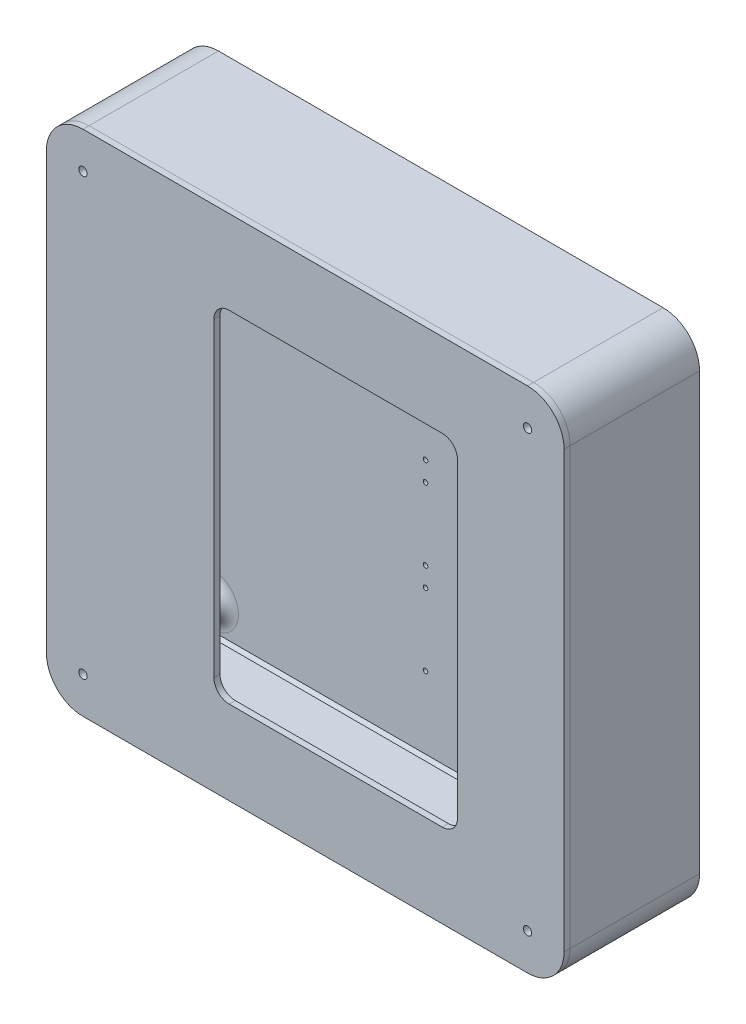
SolidWorks part; units mm, degrees
ref_plane "Front Plane" through (0, 0, 0) normal (1, 0, 0) x (0, 1, 0)
ref_plane "Top Plane" through (0, 0, 0) normal (0, 0, 1) x (0, 1, 0)
ref_plane "Right Plane" through (0, 0, 0) normal (0, 1, 0) x (-1, 0, 0)
sketch "Sketch1" plane through (0, 0, 0) normal (0, 0, 1) x (0, 1, 0)
  line L0 (-6.375, 0) -> (6.375, 0) construction
  line L1 (-113.625, 0) -> (-66.375, 0) construction
  line L2 (66.375, 0) -> (113.625, 0) construction
  line L3 (-167, 164) -> (167, 164)
  line L4 (-163, 160) -> (163, 160)
  line L5 (-163, 160) -> (-163, -172)
  line L6 (-163, -172) -> (163, -172)
  line L7 (163, 160) -> (163, -172)
  line L8 (167, 164) -> (167, -176)
  line L9 (-167, -176) -> (167, -176)
  line L10 (-167, 164) -> (-167, -176)
  line L11 (53.625, 0) -> (6.375, 0) construction
  line L12 (-6.375, 0) -> (-53.625, 0) construction
  circle A0 centre (-113.625, 0) radius 1.5
  circle A1 centre (-66.375, 0) radius 1.5
  circle A2 centre (-53.625, 0) radius 1.5
  circle A3 centre (-6.375, 0) radius 1.5
  circle A4 centre (6.375, 0) radius 1.5
  circle A5 centre (53.625, 0) radius 1.5
  circle A6 centre (66.375, 0) radius 1.5
  circle A7 centre (113.625, 0) radius 1.5
  circle A8 centre (143, -152) radius 2.1
  circle A9 centre (-143, -152) radius 2.1
  circle A10 centre (-143, 140) radius 2.1
  circle A11 centre (143, 140) radius 2.1
  circle A12 centre (143, -152) radius 7.1
  circle A13 centre (-143, -152) radius 7.1
  circle A14 centre (-143, 140) radius 7.1
  circle A15 centre (143, 140) radius 7.1
  point P3 (0, 0)
  point P4 (66.375, 0)
  point P5 (53.625, 0)
  point P6 (-53.625, 0)
  point P7 (-66.375, 0)
  point P8 (113.625, 0)
  point P9 (-113.625, 0)
  point P28 (0, 160)
  point P29 (-90, 0)
  point P30 (90, 0)
  point P35 (30, 0)
  point P36 (-30, 0)
  point P45 (0, 0)
  point P46 (0, 0)
  point P47 (0, 0)
  point P48 (0, 0)
  dimension "D8" = 3
  dimension "D13" = 4.2
  dimension "D1" = 12.75
  dimension "D2" = 60
  dimension "D3" = 60
  dimension "D4" = 60
  dimension "D5" = 60
  dimension "D6" = 60
  dimension "D7" = 60
  dimension "D10" = 172
  dimension "D9" = 73
  dimension "D11" = 160
  dimension "D14" = 20
  dimension "D15" = 20
  dimension "D16" = 20
  dimension "D17" = 20
  dimension "D12" = 4
  dimension "D18" = 5
extrude "Boss-Extrude1" add sketch "Sketch1" along normal blind 4 contours L3 L10 L9 L8 L4 L7 L6 L5 | L7 L4 L5 L6 A7 A6 A5 A4 A3 A2 A1 A0 | A12 A8 | A13 A9 | A14 A10 | A15 A11 region at (-163.5234, 0, 0) region at (6.0032, 0, 0) region at (152, 136.1008, 0) region at (152, -149.8992, 0) region at (-140, -149.8992, 0) region at (-140, 136.1008, 0)
extrude "Boss-Extrude2" add sketch "Sketch1<3>" along normal blind 85 contours L3 L10 L9 L8 L4 L7 L6 L5 region at (-163.5234, 0, 0)
sketch "Sketch1<3>" plane through (0, 0, 0) normal (0, 0, 1) x (0, 1, 0) same geometry as "Sketch1"
fillet "Fillet1" radius 20 4 edges at (-160, -163, 44.5) (172, -163, 44.5) (172, 163, 44.5) (-160, 163, 44.5)
fillet "Fillet2" radius 24 4 edges at (-164, -167, 42.5) (176, -167, 42.5) (176, 167, 42.5) (-164, 167, 42.5)
sketch "Sketch2" plane through (-164, 0, 0) normal (-1, 0, 0) x (0, -1, 0)
  line L0 (143, 0) -> (-143, 0) construction
  line L1 (-92.8983, 12.35) -> (-87.1017, 12.35)
  line L2 (-32.8983, 12.35) -> (-27.1017, 12.35)
  line L3 (27.1017, 12.35) -> (32.8983, 12.35)
  line L4 (87.1017, 12.35) -> (92.8983, 12.35)
  arc A0 (-87.1017, 12.35) -> (-92.8983, 12.35) centre (-90, 18) ccw
  arc A1 (-27.1017, 12.35) -> (-32.8983, 12.35) centre (-30, 18) ccw
  arc A2 (32.8983, 12.35) -> (27.1017, 12.35) centre (30, 18) ccw
  arc A3 (92.8983, 12.35) -> (87.1017, 12.35) centre (90, 18) ccw
  point P8 (-90, 24.35)
  point P12 (-30, 24.35)
  point P13 (30, 24.35)
  point P15 (90, 24.35)
  dimension "D1" = 18
  dimension "D2" = 12.7
  dimension "D3" = 12
sketch "Sketch3" plane through (0, -167, 0) normal (0, -1, 0) x (1, 0, 0)
  line L0 (-140, 0) -> (152, 0) construction
  line L1 (139.1017, 12.35) -> (144.8983, 12.35)
  arc A0 (144.8983, 12.35) -> (139.1017, 12.35) centre (142, 18) ccw
  point P7 (142, 24.35)
  dimension "D1" = 12.7
  dimension "D2" = 18
  dimension "D3" = 142
  dimension "D4" = 12
extrude "Boss-Extrude3" add sketch "Sketch1<4>" along normal blind 85 contours A12 A8 | A13 A9 | A14 A10 | A15 A11 region at (152, 136.1008, 0) region at (152, -149.8992, 0) region at (-140, -149.8992, 0) region at (-140, 136.1008, 0)
sketch "Sketch1<4>" plane through (0, 0, 0) normal (0, 0, 1) x (0, 1, 0) same geometry as "Sketch1"
extrude "Cut-Extrude1" cut sketch "Sketch2" against normal up to next
extrude "Cut-Extrude2" cut sketch "Sketch3" against normal up to next
sketch "Sketch4" plane through (0, 0, 4) normal (0, 0, 1) x (1, 0, 0)
  line L0 (150, 70) -> (150, -70) construction
  line L1 (162.7, 121) -> (137.3, 121)
  line L2 (162.7, 121) -> (162.7, 70)
  line L3 (162.7, 70) -> (137.3, 70)
  line L4 (137.3, 121) -> (137.3, 70)
  line L5 (162.7, -70) -> (137.3, -70)
  line L6 (162.7, -70) -> (162.7, -121)
  line L7 (162.7, -121) -> (137.3, -121)
  line L8 (137.3, -70) -> (137.3, -121)
  line L9 (132.3, 126) -> (132.3, 65)
  line L10 (167.7, 65) -> (132.3, 65)
  line L11 (167.7, 126) -> (167.7, 65)
  line L12 (167.7, 126) -> (132.3, 126)
  line L13 (132.3, -65) -> (132.3, -126)
  line L14 (167.7, -126) -> (132.3, -126)
  line L15 (167.7, -65) -> (167.7, -126)
  line L16 (167.7, -65) -> (132.3, -65)
  point P8 (150, 70)
  point P9 (150, -70)
  point P10 (150, 0)
  point P13 (0, 0)
  dimension "D1" = 51
  dimension "D2" = 25.4
  dimension "D3" = 140
  dimension "D4" = 150
  dimension "D5" = 140
  dimension "D6" = 150
  dimension "D7" = 5
extrude "Boss-Extrude4" add sketch "Sketch4" along normal blind 8
chamfer "Chamfer1" distance 2 angle 45 8 edges at (-154.1421, 157.1421, 4) (-160, 0, 4) (6, 163, 4) (-154.1421, -157.1421, 4) (166.1421, 157.1421, 4) (6, -163, 4) (172, 0, 4) (166.1421, -157.1421, 4)
fillet "Fillet3" radius 10 4 edges at (159.1, 143, 4) (-132.9, 143, 4) (-132.9, -143, 4) (159.1, -143, 4)
sketch "Sketch5" plane through (0, 0, 4) normal (0, 0, 1) x (1, 0, 0)
  line L0 (162.7, -121) -> (162.7, -70) construction
  line L1 (162.7, -70) -> (137.3, -70) construction
  line L2 (137.3, -70) -> (137.3, -121) construction
  line L3 (137.3, -121) -> (162.7, -121) construction
  line L4 (162.7, 70) -> (162.7, 121) construction
  line L5 (162.7, 121) -> (137.3, 121) construction
  line L6 (137.3, 121) -> (137.3, 70) construction
  line L7 (137.3, 70) -> (162.7, 70) construction
  line L8 (162.7, -121) -> (162.7, -70)
  line L9 (162.7, -70) -> (137.3, -70)
  line L10 (137.3, -70) -> (137.3, -121)
  line L11 (137.3, -121) -> (162.7, -121)
  line L12 (162.7, 70) -> (162.7, 121)
  line L13 (162.7, 121) -> (137.3, 121)
  line L14 (137.3, 121) -> (137.3, 70)
  line L15 (137.3, 70) -> (162.7, 70)
extrude "Cut-Extrude3" cut sketch "Sketch5" against normal blind 2
sketch "Sketch6" plane through (0, 0, 85) normal (0, 0, 1) x (1, 0, 0)
  line L0 (-140, -163) -> (152, -163) construction
  line L1 (-160, -143) -> (-160, 143) construction
  line L2 (-140, 163) -> (152, 163) construction
  line L3 (172, -143) -> (172, 143) construction
  line L4 (-164, 143) -> (-164, -143)
  line L5 (-140, -167) -> (152, -167)
  line L6 (176, -143) -> (176, 143)
  line L7 (152, 167) -> (-140, 167)
  line L8 (-164, 143) -> (-164, -143)
  line L9 (-140, -167) -> (152, -167)
  line L10 (176, -143) -> (176, 143)
  line L11 (152, 167) -> (-140, 167)
  line L12 (-140, -163) -> (152, -163)
  line L13 (-160, -143) -> (-160, 143)
  line L14 (-140, 163) -> (152, 163)
  line L15 (172, -143) -> (172, 143)
  line L16 (168, -143) -> (168, 143)
  line L17 (-140, 159) -> (152, 159)
  line L18 (-156, -143) -> (-156, 143)
  line L19 (-140, -159) -> (152, -159)
  arc A0 (152, -163) -> (172, -143) centre (152, -143) ccw construction
  arc A1 (-160, -143) -> (-140, -163) centre (-140, -143) ccw construction
  arc A2 (-140, 163) -> (-160, 143) centre (-140, 143) ccw construction
  arc A3 (172, 143) -> (152, 163) centre (152, 143) ccw construction
  arc A4 (-164, -143) -> (-140, -167) centre (-140, -143) ccw
  arc A5 (152, -167) -> (176, -143) centre (152, -143) ccw
  arc A6 (176, 143) -> (152, 167) centre (152, 143) ccw
  arc A7 (-140, 167) -> (-164, 143) centre (-140, 143) ccw
  arc A8 (-164, -143) -> (-140, -167) centre (-140, -143) ccw
  arc A9 (152, -167) -> (176, -143) centre (152, -143) ccw
  arc A10 (176, 143) -> (152, 167) centre (152, 143) ccw
  arc A11 (-140, 167) -> (-164, 143) centre (-140, 143) ccw
  arc A12 (152, -163) -> (172, -143) centre (152, -143) ccw
  arc A13 (-160, -143) -> (-140, -163) centre (-140, -143) ccw
  arc A14 (-140, 163) -> (-160, 143) centre (-140, 143) ccw
  arc A15 (172, 143) -> (152, 163) centre (152, 143) ccw
  circle A16 centre (152, 143) radius 2.75
  circle A17 centre (152, -143) radius 2.75
  circle A18 centre (-140, -143) radius 2.75
  circle A19 centre (-140, 143) radius 2.75
  arc A20 (168, 143) -> (152, 159) centre (152, 143) ccw
  arc A21 (-140, 159) -> (-156, 143) centre (-140, 143) ccw
  arc A22 (-156, -143) -> (-140, -159) centre (-140, -143) ccw
  arc A23 (152, -159) -> (168, -143) centre (152, -143) ccw
  line M9 (152, -163) -> (-140, -163)
  arc M10 (-140, -163) -> (-160, -143) centre (-140, -143) cw
  line M11 (-160, -143) -> (-160, 143)
  arc M12 (-160, 143) -> (-140, 163) centre (-140, 143) cw
  line M13 (-140, 163) -> (152, 163)
  arc M14 (152, 163) -> (172, 143) centre (152, 143) cw
  line M15 (172, 143) -> (172, -143)
  arc M16 (172, -143) -> (152, -163) centre (152, -143) cw
  line M17 (-164, 143) -> (-164, -143)
  arc M18 (-164, -143) -> (-140, -167) centre (-140, -143) ccw
  line M19 (-140, -167) -> (152, -167)
  arc M20 (152, -167) -> (176, -143) centre (152, -143) ccw
  line M21 (176, -143) -> (176, 143)
  arc M22 (176, 143) -> (152, 167) centre (152, 143) ccw
  line M23 (152, 167) -> (-140, 167)
  arc M24 (-140, 167) -> (-164, 143) centre (-140, 143) ccw
  dimension "D2" = 5.5
  dimension "D1" = 0
  dimension "D3" = 4
extrude "Boss-Extrude5" add sketch "Sketch6" along normal blind 4 separate body contours L19 A23 L16 A20 L17 A21 L18 A22 A16 A17 A18 A19 | A23 L19 A22 L18 A21 L17 A20 L16 M9 M16 M15 M14 M13 M12 M11 M10 | M24 M17 M18 M19 M20 M21 M22 M23 M16 M9 M10 M11 M12 M13 M14 M15 region at (-156.6335, 159.6335, 85) region at (-153.8131, -156.8131, 85) region at (6, 0, 85)
sketch "Sketch7" plane through (0, 0, 89) normal (0, 0, 1) x (1, 0, 0)
  line L0 (-164, 143) -> (-164, -143) construction
  line L1 (106, 112) -> (-54, 112)
  line L2 (106, 112) -> (106, -112)
  line L3 (106, -112) -> (-54, -112)
  line L4 (-54, 112) -> (-54, -112)
  line L5 (-140, -167) -> (152, -167) construction
  line L6 (176, -143) -> (176, 143) construction
  point P6 (-54, 0)
  point P7 (0, 0)
  dimension "D1" = 110
  dimension "D2" = 55
  dimension "D3" = 70
extrude "Cut-Extrude4" cut sketch "Sketch7" against normal up to next (4 mm away)
extrude "Boss-Extrude6" add sketch "Sketch6<3>" against normal blind 5 contours A23 L19 A22 L18 A21 L17 A20 L16 M9 M16 M15 M14 M13 M12 M11 M10 region at (-153.8131, -156.8131, 85)
sketch "Sketch6<3>" plane through (0, 0, 85) normal (0, 0, 1) x (1, 0, 0) same geometry as "Sketch6"
fillet "Fillet4" radius 10 4 edges at (-54, -112, 87) (-54, 112, 87) (106, 112, 87) (106, -112, 87)
equation "\"D15@Sketch1\"=\"D14@Sketch1\""
equation "\"D16@Sketch1\"=\"D14@Sketch1\""
equation "\"D17@Sketch1\"=\"D14@Sketch1\""
